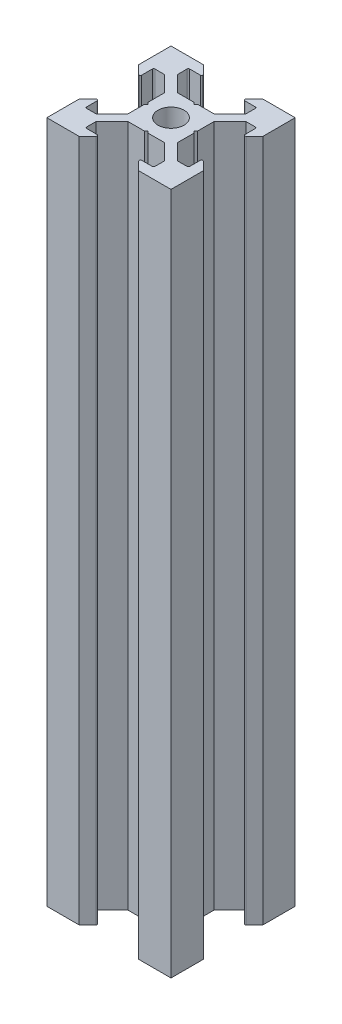
SolidWorks part; units mm, degrees
ref_plane "Plan de face" through (0, 0, 0) normal (0, 0, 1) x (1, 0, 0)
ref_plane "Plan de dessus" through (0, 0, 0) normal (0, 1, 0) x (1, 0, 0)
ref_plane "Plan de droite" through (0, 0, 0) normal (1, 0, 0) x (0, 0, -1)
sketch "Esquisse1" plane through (0, 0, 0) normal (0, 0, 1) x (1, 0, 0)
  line L1 (-10, -55) -> (10, -55)
  line L2 (-10, -55) -> (-10, 55)
  line L3 (-10, 55) -> (10, 55)
  line L4 (10, -55) -> (10, 55)
  line L5 (-10, -55) -> (10, 55) construction
  line L6 (-10, 55) -> (10, -55) construction
  point P0 (0, 0)
  dimension "D1" = 20
  dimension "D2" = 110
extrude "Boss.-Extru.1" add sketch "Esquisse1" along normal blind 10 and the other way blind 10
sketch "Esquisse2" plane through (0, 55, 0) normal (0, 1, 0) x (1, 0, 0)
  line L0 (0, 10) -> (0, -10) construction
  line L1 (-10, -10) -> (10, -10)
  line L2 (-10, -10) -> (-10, 10)
  line L3 (-10, 10) -> (10, 10)
  line L4 (10, -10) -> (10, 10)
  line L5 (-10, -10) -> (10, 10) construction
  line L6 (-10, 10) -> (10, -10) construction
  line L7 (-10, 0) -> (10, 0) construction
  line L8 (-4.8, 10) -> (-3.4414, 8.6414)
  line L9 (-10, 5.5) -> (10, 5.5) construction
  line L10 (-5.5, -10) -> (-5.5, 10) construction
  line L11 (5.5, -10) -> (5.5, 10) construction
  line L12 (-10, -5.5) -> (10, -5.5) construction
  line L13 (-3.1, -8.3) -> (-3.1, -10) construction
  line L14 (3.1, -8.3) -> (3.1, -10) construction
  line L15 (-10, -8.3) -> (10, -8.3) construction
  line L16 (-8.3, 10) -> (-8.3, -10) construction
  line L17 (2.9393, -4) -> (-2.9393, -4)
  line L18 (4, -2.9393) -> (4, 2.9393)
  line L19 (2.9393, 4) -> (-2.9393, 4)
  line L20 (-4, -2.9393) -> (-4, 2.9393)
  line L21 (4, -4) -> (-4, 4) construction
  line L22 (4, 4) -> (-4, -4) construction
  line L23 (-3.4414, -8.6414) -> (-4.8, -10)
  line L24 (-3.5828, 8.3) -> (-5.3, 8.3)
  line L25 (-10, -4.8) -> (-8.6414, -3.4414)
  line L26 (-8.3, -3.5828) -> (-8.3, -5.3)
  line L27 (-3.5828, -8.3) -> (-5.3, -8.3)
  line L28 (-8.1, -5.5) -> (-6.5607, -5.5)
  line L29 (-5.5, -6.5607) -> (-5.5, -8.1)
  line L30 (-5.5, -6.5607) -> (-2.9393, -4)
  line L31 (-6.5607, -5.5) -> (-4, -2.9393)
  line L32 (-5.5, 8.1) -> (-5.5, 6.5607)
  line L33 (-10.5303, -9.4697) -> (9.4697, 10.5303) construction
  line L34 (-9.4697, -10.5303) -> (10.5303, 9.4697) construction
  line L35 (-5.5, 6.5607) -> (-2.9393, 4)
  line L36 (-6.5607, 5.5) -> (-4, 2.9393)
  line L37 (-6.5607, 5.5) -> (-8.1, 5.5)
  line L38 (-8.3, 3.5828) -> (-8.3, 5.3)
  line L39 (-8.6414, 3.4414) -> (-10, 4.8)
  line L40 (10, 4.8) -> (8.6414, 3.4414)
  line L41 (8.3, 3.5828) -> (8.3, 5.3)
  line L42 (8.1, 5.5) -> (6.5607, 5.5)
  line L43 (6.5607, 5.5) -> (4, 2.9393)
  line L44 (5.5, 6.5607) -> (2.9393, 4)
  line L45 (5.5, 6.5607) -> (5.5, 8.1)
  line L46 (3.5828, 8.3) -> (5.3, 8.3)
  line L47 (3.4414, 8.6414) -> (4.8, 10)
  line L48 (4.8, -10) -> (3.4414, -8.6414)
  line L49 (3.5828, -8.3) -> (5.3, -8.3)
  line L50 (5.5, -8.1) -> (5.5, -6.5607)
  line L51 (5.5, -6.5607) -> (2.9393, -4)
  line L52 (6.5607, -5.5) -> (4, -2.9393)
  line L53 (6.5607, -5.5) -> (8.1, -5.5)
  line L54 (8.3, -3.5828) -> (8.3, -5.3)
  line L55 (8.6414, -3.4414) -> (10, -4.8)
  line L56 (-4, 0.2828) -> (-3.7172, 0)
  line L57 (-3.7172, 0) -> (-4, -0.2828)
  line L58 (0.2828, 4) -> (0, 3.7172)
  line L59 (0, 3.7172) -> (-0.2828, 4)
  line L60 (4, -0.2828) -> (3.7172, 0)
  line L61 (3.7172, 0) -> (4, 0.2828)
  line L62 (-0.2828, -4) -> (0, -3.7172)
  line L63 (0, -3.7172) -> (0.2828, -4)
  circle A0 centre (0, 0) radius 2.1
  arc A1 (-8.3, -3.5828) -> (-8.6414, -3.4414) centre (-8.5, -3.5828) ccw
  arc A2 (-3.5828, -8.3) -> (-3.4414, -8.6414) centre (-3.5828, -8.5) cw
  arc A3 (8.3, -3.5828) -> (8.6414, -3.4414) centre (8.5, -3.5828) cw
  arc A4 (8.6414, 3.4414) -> (8.3, 3.5828) centre (8.5, 3.5828) cw
  arc A5 (3.5828, 8.3) -> (3.4414, 8.6414) centre (3.5828, 8.5) cw
  arc A6 (-3.4414, 8.6414) -> (-3.5828, 8.3) centre (-3.5828, 8.5) cw
  arc A7 (-8.3, 3.5828) -> (-8.6414, 3.4414) centre (-8.5, 3.5828) cw
  arc A8 (-8.1, 5.5) -> (-8.3, 5.3) centre (-8.1, 5.3) ccw
  arc A9 (-5.3, 8.3) -> (-5.5, 8.1) centre (-5.3, 8.1) ccw
  arc A10 (5.5, 8.1) -> (5.3, 8.3) centre (5.3, 8.1) ccw
  arc A11 (8.3, 5.3) -> (8.1, 5.5) centre (8.1, 5.3) ccw
  arc A12 (8.1, -5.5) -> (8.3, -5.3) centre (8.1, -5.3) ccw
  arc A13 (5.3, -8.3) -> (5.5, -8.1) centre (5.3, -8.1) ccw
  arc A14 (-5.3, -8.3) -> (-5.5, -8.1) centre (-5.3, -8.1) cw
  arc A15 (-8.3, -5.3) -> (-8.1, -5.5) centre (-8.1, -5.3) ccw
  arc A16 (3.4414, -8.6414) -> (3.5828, -8.3) centre (3.5828, -8.5) cw
  point P0 (0, 0)
  point P16 (0, -8.3)
  point P19 (0, -4.9968)
  point P81 (-8.3, -3.1)
  point P109 (-5.5, -8.3)
  dimension "D1" = 4.2
  dimension "D15" = 0.2
  dimension "D2" = 0.2
  dimension "D3" = 11
  dimension "D4" = 4.5
  dimension "D5" = 4.5
  dimension "D6" = 11
  dimension "D7" = 6
  dimension "D8" = 4.3
  dimension "D9" = 4.3
  dimension "D10" = 45
  dimension "D11" = 45
  dimension "D17" = 0.4
  dimension "D16" = 0.4
  dimension "D12" = 0.75
  dimension "D13" = 0.75
  dimension "D14" = 4
  dimension "D18" = 4
extrude "Enlèv. mat.-Extru.1" cut sketch "Esquisse2" against normal through all contours A0 | L46 L47 L3 L8 L24 L32 L35 L19 L44 L45 | L38 L39 L2 L25 L26 L28 L31 L20 L36 L37 | L54 L55 L4 L40 L41 L42 L43 L18 L52 L53 | L50 L51 L17 L30 L29 L27 L23 L1 L48 L49 | L57 L56 L20 | L59 L58 L19 | L61 L60 L18 | L63 L62 L17 region at (0, 55, 7.0678) region at (-7.0678, 55, 0) region at (7.0678, 55, 0) region at (0, 55, -7.0678) region at (0, 55, 3.9057) region at (-3.9057, 55, 0) region at (3.9057, 55, 0) region at (0, 55, -3.9057) region at (0, 55, 0)
equation "\"D5@Esquisse2\"=\"D4@Esquisse2\""
equation "\"D6@Esquisse2\"=\"D3@Esquisse2\""
equation "\"D16@Esquisse2\"=\"D17@Esquisse2\""
